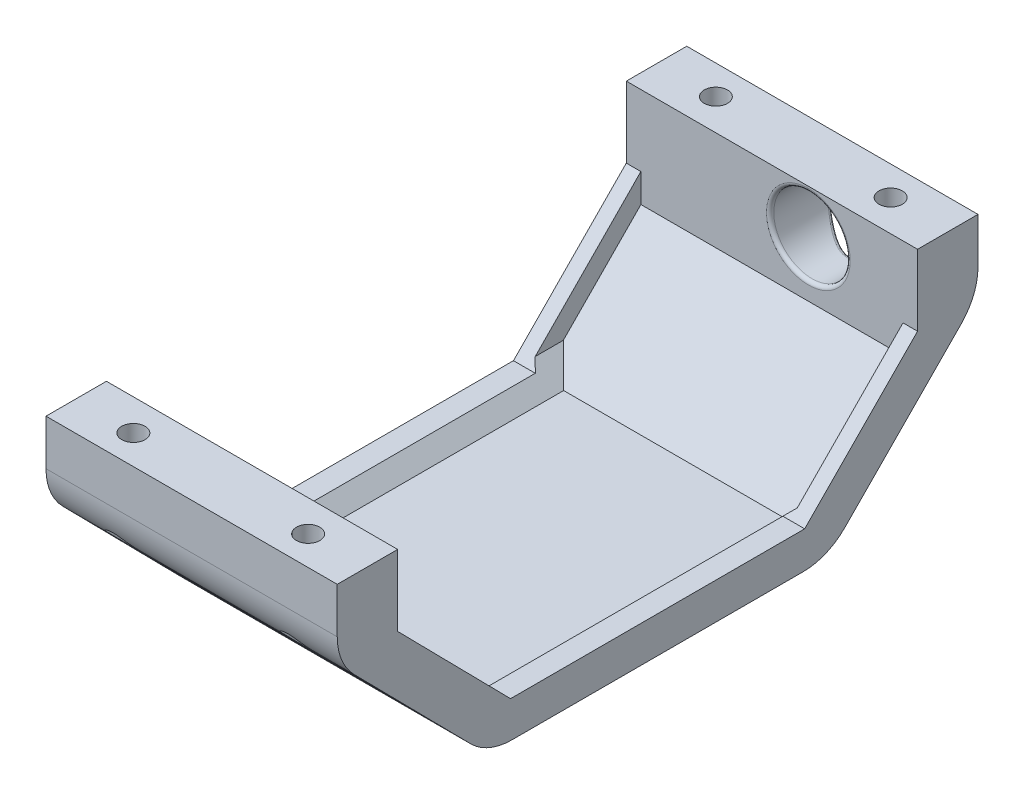
SolidWorks part; units mm, degrees
ref_plane "Alzado" through (0, 0, 0) normal (0, 0, 1) x (1, 0, 0)
ref_plane "Planta" through (0, 0, 0) normal (0, 1, 0) x (1, 0, 0)
ref_plane "Vista lateral" through (0, 0, 0) normal (1, 0, 0) x (0, 0, -1)
sketch "Croquis1" plane through (0, 0, 0) normal (0, 1, 0) x (1, 0, 0)
  line L0 (0, 0) -> (0, 50000) construction
  line L1 (-20, 44) -> (20, 44)
  line L2 (-20, 44) -> (-20, -44)
  line L3 (-20, -44) -> (20, -44)
  line L4 (20, 44) -> (20, -44)
  line L5 (-20, 44) -> (20, -44) construction
  line L6 (-20, -44) -> (20, 44) construction
  line L7 (0, 0) -> (50000, 0) construction
  circle A0 centre (-12, 40) radius 1.6
  circle A1 centre (12, 40) radius 1.6
  circle A2 centre (-12, -40) radius 1.6
  circle A3 centre (12, -40) radius 1.6
  point P0 (0, 0)
  dimension "D4" = 3.2
  dimension "D1" = 40
  dimension "D2" = 88
  dimension "D3" = 24
  dimension "D5" = 4
extrude "Saliente-Extruir1" add sketch "Croquis1" along normal blind 30.5
sketch "Croquis2" plane through (0, 30.5, 0) normal (0, 1, 0) x (1, 0, 0)
  line L0 (20, -44) -> (20, 44) construction
  line L1 (-13, 24) -> (10.2, 24) construction
  line L2 (-13, 24) -> (-13, -27.4) construction
  line L3 (-13, -27.4) -> (10.2, -27.4) construction
  line L4 (10.2, 24) -> (10.2, -27.4) construction
  line L5 (-13, 24) -> (10.2, -27.4) construction
  line L6 (-13, -27.4) -> (10.2, 24) construction
  line L7 (0.6, 54.7934) -> (9.4, 54.7934) construction
  line L8 (0.6, 54.7934) -> (0.6, 9.4014) construction
  line L9 (0.6, 9.4014) -> (9.4, 9.4014) construction
  line L10 (9.4, 54.7934) -> (9.4, 9.4014) construction
  line L11 (0.6, 54.7934) -> (9.4, 9.4014) construction
  line L12 (0.6, 9.4014) -> (9.4, 54.7934) construction
  line L13 (20, 44) -> (-20, 44) construction
  point P4 (-1.4, -1.7)
  point P9 (5, 32.0974)
  dimension "D1" = 51.4
  dimension "D2" = 23.2
  dimension "D3" = 0.8
  dimension "D4" = 8.8
  dimension "D5" = 15
  dimension "D6" = 20
sketch "Croquis3" plane through (0, 30.5, 0) normal (0, 1, 0) x (1, 0, 0)
  line L0 (-20, 44) -> (-20, -44) construction
  line L1 (-20, 37) -> (20, 37)
  line L2 (-20, 37) -> (-20, -37)
  line L3 (-20, -37) -> (20, -37)
  line L4 (20, 37) -> (20, -37)
  line L5 (-20, 37) -> (20, -37) construction
  line L6 (-20, -37) -> (20, 37) construction
  line L7 (20, -44) -> (20, 44) construction
  line L8 (20, 44) -> (-20, 44) construction
  point P4 (0, 0)
  dimension "D1" = 7
ref_plane "Plano1" through (-1.4, 0, 0) normal (1, 0, 0) x (0, 0, -1)
sketch "Croquis7" plane through (0, 0, -44) normal (0, 0, -1) x (-1, 0, 0)
  line L2 (14.1255, 29.1561) -> (7.3275, 29.1561) construction
  line L3 (14.1255, 29.1561) -> (14.1255, 24.9647) construction
  line L4 (14.1255, 24.9647) -> (7.3275, 24.9647) construction
  line L5 (7.3275, 29.1561) -> (7.3275, 24.9647) construction
  line L6 (14.1255, 29.1561) -> (7.3275, 24.9647) construction
  line L7 (14.1255, 24.9647) -> (7.3275, 29.1561) construction
  text T0 "12V"
  point P0 (14.1255, 29.1561)
  point P8 (10.7265, 27.0604)
extrude "Cortar-Extruir4" cut sketch "Croquis7" against normal blind 1
sketch "Croquis8" plane through (0, 0, 0) normal (0, -1, 0) x (1, 0, 0)
  circle A0 centre (-12, 40) radius 2.8
  circle A1 centre (12, 40) radius 2.8
  circle A2 centre (-12, -40) radius 2.8
  circle A3 centre (12, -40) radius 2.8
  dimension "D1" = 5.6
extrude "Cortar-Extruir5" cut sketch "Croquis8" against normal offset from surface (20.5 mm away) 10 up to face at (-12, 30.5, 38.4)
sketch "Croquis9" plane through (20, 0, 0) normal (1, 0, 0) x (0, 0, -1)
  line L0 (0, 0) -> (0, 50000) construction
  line L1 (20, 0) -> (-20, 0)
  line L2 (-44, 0) -> (44, 0) construction
  line L3 (-25.7009, 2.3876) -> (-41.7009, 18.6399)
  line L4 (-44, 30.5) -> (-44, 0) construction
  line L5 (-44, 24.2523) -> (-44, 30.5)
  line L6 (-44, 30.5) -> (44, 30.5)
  line L8 (44, 24.2523) -> (44, 30.5)
  line L9 (25.7009, 2.3876) -> (41.7009, 18.6399)
  arc A0 (-20, 0) -> (-25.7009, 2.3876) centre (-20, 8) cw
  arc A1 (-41.7009, 18.6399) -> (-44, 24.2523) centre (-36, 24.2523) cw
  arc A2 (41.7009, 18.6399) -> (44, 24.2523) centre (36, 24.2523) ccw
  arc A3 (20, 0) -> (25.7009, 2.3876) centre (20, 8) ccw
  point P17 (0, 0)
  point P25 (0, 30.5)
  dimension "D2" = 8
  dimension "D3" = 8
  dimension "D1" = 40
extrude "Cortar-Extruir6" cut sketch "Croquis9" against normal through all flip side to cut
sketch "Croquis11" plane through (20, 0, 0) normal (1, 0, 0) x (0, 0, -1)
  line L0 (-35.7, 30.5) -> (-35.7, 16.8205)
  line L1 (-44, 30.5) -> (44, 30.5) construction
  line L2 (-35.7, 16.8205) -> (-22.094, 3)
  line L3 (-22.094, 3) -> (22.094, 3)
  line L4 (22.094, 3) -> (35.7, 16.8205)
  line L5 (35.7, 16.8205) -> (35.7, 30.5)
  line L6 (34.2173, 30.5) -> (-34.8586, 30.5) construction
  line L7 (0, 0) -> (0, 26.6558) construction
  line L10 (-41.7009, 18.6399) -> (-25.7009, 2.3876) construction
  line L11 (-20, 0) -> (20, 0) construction
  line L12 (-37.2, 14.068) -> (-37.2, 20.5) construction
  point P11 (0, 3)
  dimension "D1" = 3
  dimension "D2" = 3
  dimension "D3" = 1.5
extrude "Cortar-Extruir7" cut sketch "Croquis11" against normal through all and the other way through all
sketch "Croquis6" plane through (0, 0, -44) normal (0, 0, -1) x (-1, 0, 0)
  line L1 (-20, 30.5) -> (20, 30.5) construction
  circle A0 centre (-5, 24.5) radius 5.25
  dimension "D2" = 10.5
  dimension "D1" = 6
extrude "Cortar-Extruir3" cut sketch "Croquis6" against normal up to next
sketch "Croquis12" plane through (-20, 0, 0) normal (-1, 0, 0) x (0, 0, 1)
  line L0 (-35.7, 20.746) -> (-20.1984, 5)
  line L1 (-35.7, 30.5) -> (-35.7, 16.8205) construction
  line L2 (-20.1984, 5) -> (20.1984, 5)
  line L3 (20.1984, 5) -> (35.7, 20.746)
  line L4 (35.7, 16.8205) -> (35.7, 30.5) construction
  line L5 (35.7, 20.746) -> (35.7, 16.8205)
  line L6 (35.7, 16.8205) -> (22.094, 3)
  line L7 (22.094, 3) -> (-22.094, 3)
  line L8 (-22.094, 3) -> (-35.7, 16.8205)
  line L9 (-35.7, 16.8205) -> (-35.7, 20.746)
  line L10 (-20, 0) -> (20, 0) construction
  dimension "D1" = 5
extrude "Saliente-Extruir2" add sketch "Croquis12" against normal blind 2
chamfer "Chaflán1" distance 3 angle 45 1 edges at (-18, 3, 0)
mirror "Simetría1" about plane through (0, 0, 0) normal (1, 0, 0) of "Chaflán1", "Saliente-Extruir2"
fillet "Redondeo1" radius 0.5 3 edges at (10.25, 24.5, -35.7) (5, 29.75, -44) (5.0823, 19.2506, -42.2437)
